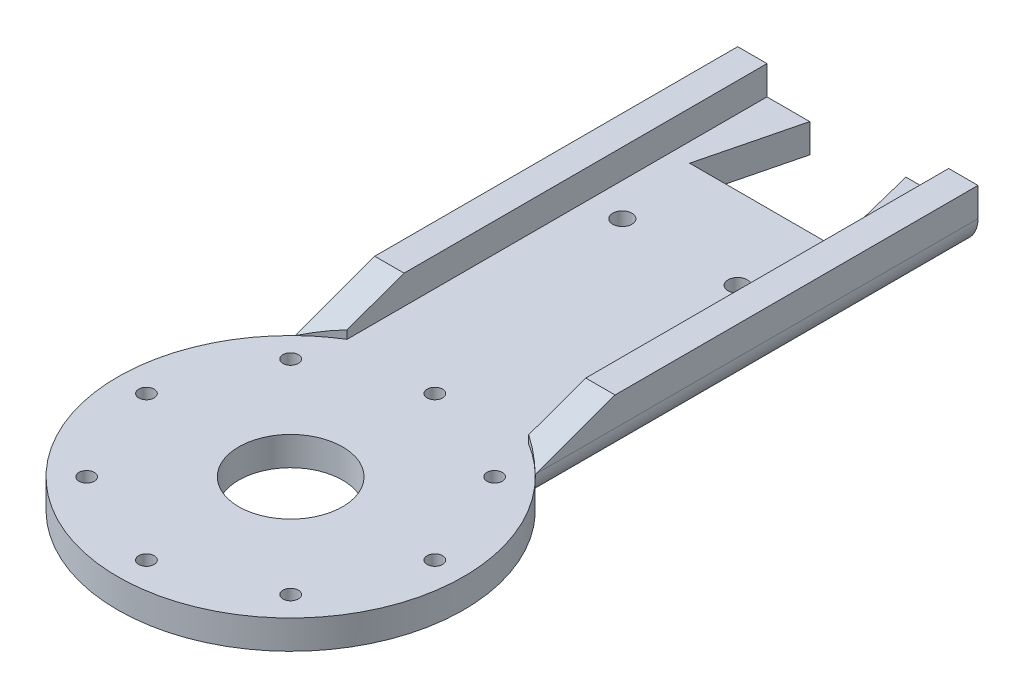
SolidWorks part; units mm, degrees
ref_plane "Alzado" through (0, 0, 0) normal (0, 0, 1) x (1, 0, 0)
ref_plane "Planta" through (0, 0, 0) normal (0, 1, 0) x (1, 0, 0)
ref_plane "Vista lateral" through (0, 0, 0) normal (1, 0, 0) x (0, 0, -1)
sketch "Croquis1" plane through (0, 0, 0) normal (0, 1, 0) x (1, 0, 0)
  line L0 (-12.2731, 38.8404) -> (-4.7731, 38.8404)
  line L1 (-4.7731, 38.8404) -> (-7.2731, 28.8404)
  line L2 (-7.2731, 28.8404) -> (7.7269, 28.8404)
  line L3 (7.7269, 28.8404) -> (5.2269, 38.8404)
  line L4 (5.2269, 38.8404) -> (12.7269, 38.8404)
  line L5 (12.7269, 38.8404) -> (12.7269, -7.2163)
  line L6 (-12.2731, 38.8404) -> (-12.2731, -7.2163)
  arc A0 (-12.2731, -7.2163) -> (12.7269, -7.2163) centre (0.2269, -20.1632) ccw
  circle A1 centre (0.2269, -20.1596) radius 5.4
  circle A2 centre (6.2269, 20.3404) radius 1
  circle A3 centre (-5.7731, 20.3404) radius 1
  circle A4 centre (0.2269, -5.1596) radius 0.8
  circle A5 centre (10.8361, -9.5541) radius 0.8
  circle A6 centre (15.2305, -20.1632) radius 0.8
  circle A7 centre (10.8361, -30.7724) radius 0.8
  circle A8 centre (0.2269, -35.1668) radius 0.8
  circle A9 centre (-10.3822, -30.7724) radius 0.8
  circle A10 centre (-14.7767, -20.1632) radius 0.8
  circle A11 centre (-10.3822, -9.5541) radius 0.8
  point P31 (0.2269, -20.1632)
extrude "Saliente-Extruir1" add sketch "Croquis1" along normal blind 3
sketch "Croquis2" plane through (0, 3, 0) normal (0, 1, 0) x (1, 0, 0)
  line L0 (0.2269, 28.8404) -> (0.2269, -45.8505) construction
  line L1 (-12.2731, 38.8404) -> (-9.2231, 38.8404)
  line L2 (-12.2731, 38.8404) -> (-12.2731, -7.2163)
  line L4 (-9.2231, 38.8404) -> (-9.2231, -4.847)
  line L5 (7.7269, 28.8404) -> (-7.2731, 28.8404) construction
  line L6 (9.6769, 38.8404) -> (9.6769, -4.847)
  line L8 (12.7269, 38.8404) -> (12.7269, -7.2163)
  line L9 (12.7269, 38.8404) -> (9.6769, 38.8404)
  arc A0 (-9.2231, -4.847) -> (-12.2731, -7.2163) centre (0.2269, -20.1596) ccw
  arc A1 (12.7269, -7.2163) -> (9.6769, -4.847) centre (0.2269, -20.1596) ccw
  dimension "D1" = 3.05
extrude "Saliente-Extruir2" add sketch "Croquis2" along normal blind 3
sketch "Croquis3" plane through (-12.2731, 0, 0) normal (-1, 0, 0) x (0, 0, 1)
  line L0 (-1.0837, 6) -> (7.2163, 3)
  line L1 (-38.8404, 6) -> (7.2163, 6) construction
  line L2 (7.2163, 3) -> (7.2163, 6)
  line L3 (7.2163, 6) -> (-1.0837, 6)
  dimension "D1" = 8.3
extrude "Cortar-Extruir1" cut sketch "Croquis3" against normal blind 42
fillet "Redondeo1" radius 3 2 edges at (12.7269, 0, -15.812) (-12.2731, 0, -15.812)
